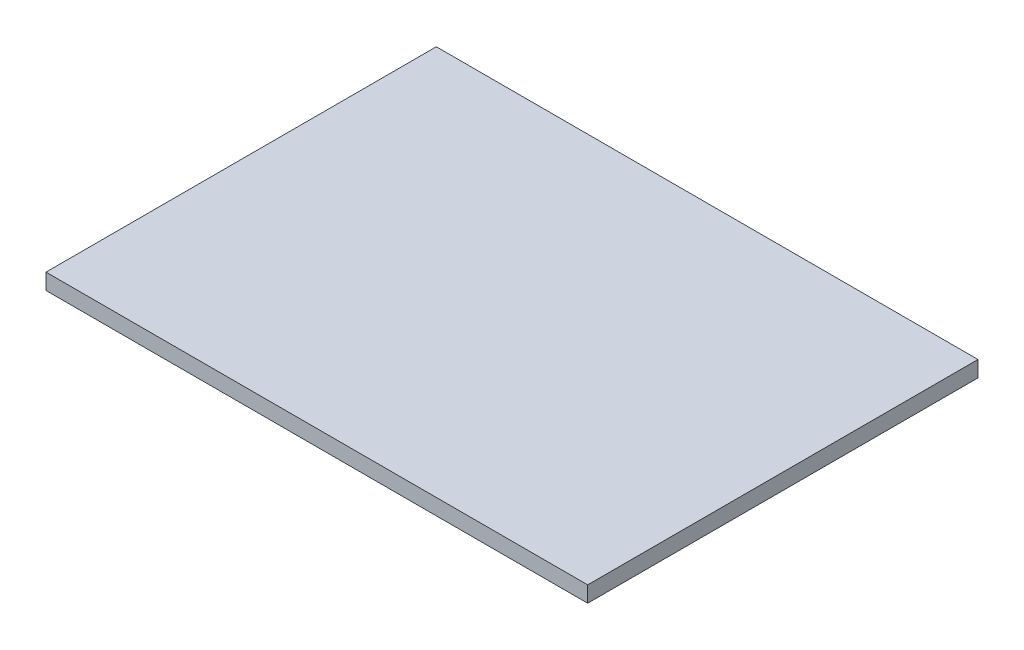
SolidWorks part; units mm, degrees
ref_plane "Front Plane" through (0, 0, 0) normal (0, 0, 1) x (1, 0, 0)
ref_plane "Top Plane" through (0, 0, 0) normal (0, 1, 0) x (1, 0, 0)
ref_plane "Right Plane" through (0, 0, 0) normal (1, 0, 0) x (0, 0, -1)
sketch "Sketch1" plane through (0, 0, 0) normal (0, 1, 0) x (1, 0, 0)
  line L1 (-170, -122.5) -> (170, -122.5)
  line L2 (-170, -122.5) -> (-170, 122.5)
  line L3 (-170, 122.5) -> (170, 122.5)
  line L4 (170, -122.5) -> (170, 122.5)
  line L5 (-170, -122.5) -> (170, 122.5) construction
  line L6 (-170, 122.5) -> (170, -122.5) construction
  point P0 (0, 0)
  dimension "D1" = 340
  dimension "D2" = 245
extrude "Boss-Extrude1" add sketch "Sketch1" along normal blind 10
equation "\"PCWidth\"= 172mm"
equation "\"PCLength\"= 320mm"
equation "\"PCHeight\"= 242mm"
equation "\"WallThickness\"= 10mm"
equation "\"ThermoBarrierThickness\"= 3mm"
equation "\"HotSideGap\"= 50mm"
equation "\"D1@Sketch1\"=\"PCLength\" + (2 * \"WallThickness\")"
equation "\"D2@Sketch1\"=\"PCWidth\" + \"ThermoBarrierThickness\" + \"HotSideGap\" + (2 * \"WallThickness\")"
equation "\"D1@Boss-Extrude1\"=\"WallThickness\""
equation "\"PCClearance\"= 25mm"
equation "\"RadiatorHeight\"= 275mm"
